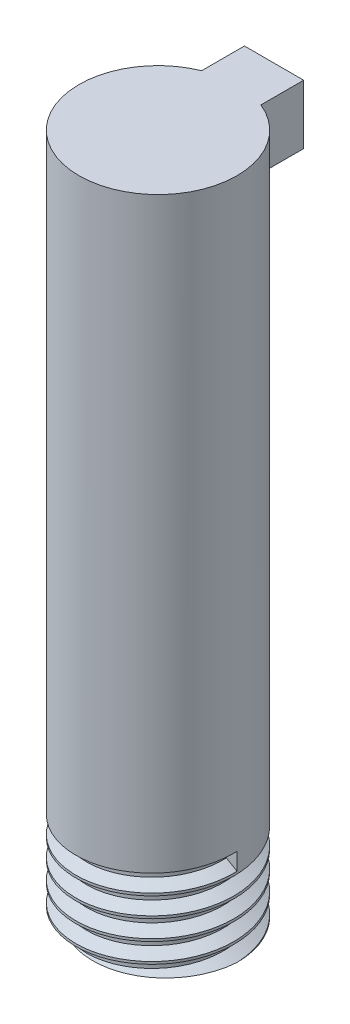
SolidWorks part; units mm, degrees
ref_plane "Front Plane" through (0, 0, 0) normal (0, 0, 1) x (1, 0, 0)
ref_plane "Top Plane" through (0, 0, 0) normal (0, 1, 0) x (1, 0, 0)
ref_plane "Right Plane" through (0, 0, 0) normal (1, 0, 0) x (0, 0, -1)
sketch "Sketch2" plane through (0, 0, 0) normal (0, 1, 0) x (1, 0, 0)
  circle A0 centre (0, 0) radius 4
  dimension "D1" = 8
extrude "Boss-Extrude1" add sketch "Sketch2" along normal blind 30.5
sketch "Sketch5" plane through (0, 0, 0) normal (0, -1, 0) x (1, 0, 0)
  circle A0 centre (0, 0) radius 4
extrude "Boss-Extrude3" add sketch "Sketch5" along normal blind 4
thread "Thread1" pitch 1 method cut profile "Thread Profile1" start angle 0, offset 1, length 5, pitch 1, diameter 8
ref_plane "Plane1" through (4, -5, 0) normal (0, 0, 1) x (1, 0, 0)
sketch "Thread Profile1" plane through (4, -5, 0) normal (0, 0, 1) x (1, 0, 0)
  line L0 (0, 0) -> (0, 1) construction
  line L11 (0, 0) -> (0, 0.875)
  line L12 (0, 0.875) -> (-0.5413, 0.5625)
  line L13 (-0.5413, 0.5625) -> (-0.5413, 0.3125)
  line L15 (-0.5413, 0.3125) -> (0, 0)
  line L17 (-0.5413, 0.4375) -> (0, 0.4375) construction
  point P2 (0, 0)
  dimension "Pitch" = 1
  dimension "Profile_Angle" = 60
  dimension "Profile_Land" = 0.25
  dimension "Profile_Height" = 0.5413
sketch "Sketch7" plane through (0, 30.5, 0) normal (0, 1, 0) x (1, 0, 0)
  line L0 (-1.5, 4) -> (-1.5, 2.871)
  line L3 (-1.5, 5.875) -> (1.5, 5.875)
  line L4 (1.5, 4) -> (1.5, 5.875)
  line L6 (1.5, 4) -> (1.5, 2.871)
  line L7 (1.5, 2.871) -> (-1.5, 2.871)
  line L9 (-1.5, 4) -> (-1.5, 5.875)
extrude "Boss-Extrude4" add sketch "Sketch7" against normal blind 3
